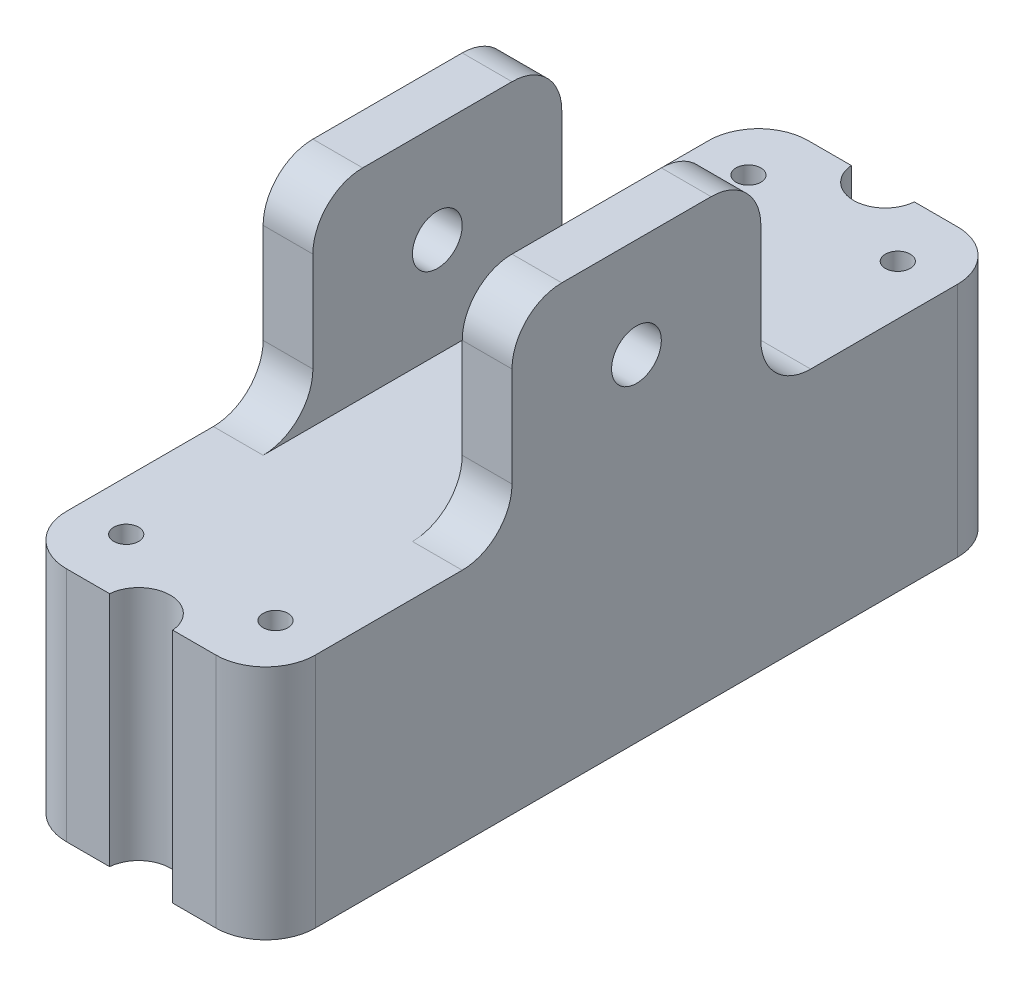
SolidWorks part; units mm, degrees
material "Nylon 101"
ref_plane "Front" through (0, 0, 0) normal (0, 0, 1) x (1, 0, 0)
ref_plane "Top" through (0, 0, 0) normal (0, 1, 0) x (1, 0, 0)
ref_plane "Right" through (0, 0, 0) normal (1, 0, 0) x (0, 0, -1)
sketch "Sketch1" plane through (0, 0, 0) normal (0, 1, 0) x (1, 0, 0)
  line L0 (-25, -75) -> (25, -75) construction
  line L1 (-15, 62.5) -> (15, 62.5) construction
  line L2 (0, -75) -> (0, 75) construction
  line L3 (-25, -75) -> (-25, 75)
  line L4 (25, -75) -> (25, 75)
  line L5 (25, 0) -> (0, 0) construction
  line L6 (25, 17) -> (97.2, 17)
  line L7 (25, 17) -> (25, -17)
  line L8 (25, -17) -> (97.2, -17)
  line L9 (97.2, 17) -> (97.2, -17)
  line L10 (-15, 62.5) -> (-15, -62.5) construction
  line L11 (-15, -62.5) -> (15, -62.5) construction
  line L12 (15, 62.5) -> (15, -62.5) construction
  line L13 (-25, -75.5) -> (25, -75.5)
  line L14 (-25, -74.5) -> (25, -74.5)
  line L15 (-25, 75.5) -> (25, 75.5)
  line L16 (-25, 74.5) -> (25, 74.5)
  circle A0 centre (0, 75) radius 6.35
  circle A1 centre (0, -75) radius 6.35
  arc A2 (-25, -75) -> (25, -75) centre (0, -75) ccw
  arc A3 (25, 75) -> (-25, 75) centre (0, 75) ccw
  circle A6 centre (-15, 62.5) radius 2.5
  circle A7 centre (-15, -62.5) radius 2.5
  circle A8 centre (15, -62.5) radius 2.5
  circle A9 centre (15, 62.5) radius 2.5
  point P8 (0, 0)
  point P24 (0, -62.5)
  dimension "D2" = 12.7
  dimension "D5" = 25
  dimension "D1" = 5
  dimension "D3" = 150
  dimension "D4" = 12.5
  dimension "D6" = 12.5
  dimension "D7" = 34
  dimension "D8" = 72.2
  dimension "D9" = 30
  dimension "D10" = 0.5
  dimension "D11" = 0.5
extrude "Boss-Extrude1" add sketch "Sketch1" along normal blind 10 and the other way blind 37.5 contours A1 L14 L4 L16 A0 L3 A9 A8 A7 A6 region at (0, 0, 0)
sketch "Sketch2" plane through (0, 0, 0) normal (0, 1, 0) x (1, 0, 0)
  line L0 (25, -75) -> (25, 75) construction
  line L1 (25, 25) -> (15, 25)
  line L2 (25, 25) -> (25, -25)
  line L3 (25, -25) -> (15, -25)
  line L4 (15, 25) -> (15, -25)
  line L6 (25, 0) -> (0, 0) construction
  line L7 (25, 0) -> (0, 0) construction
  line L8 (-25, -74.5) -> (-25, 74.5) construction
  line L9 (-25, 25) -> (-15, 25)
  line L10 (-25, 25) -> (-25, -25)
  line L11 (-25, -25) -> (-15, -25)
  line L12 (-15, 25) -> (-15, -25)
  line L13 (0, 0) -> (0, 4.5574) construction
  dimension "D1" = 50
  dimension "D2" = 10
extrude "Boss-Extrude2" add sketch "Sketch2" along normal blind 50
sketch "Sketch4" plane through (25, 0, 0) normal (1, 0, 0) x (0, 0, -1)
  line L0 (-25, 10) -> (25, 10) construction
  line L1 (-74.5, 10) -> (-25, 10) construction
  line L2 (-25, 50) -> (-25, 10) construction
  line L3 (0, 10) -> (0, 50) construction
  line L4 (-25, 50) -> (25, 50) construction
  circle A0 centre (0, 30) radius 5
  dimension "D1" = 10
extrude "Cut-Extrude2" cut sketch "Sketch4" against normal through all
fillet "Fillet1" radius 10 12 edges at (-20, 50, -25) (-20, 50, 25) (-20, 10, 25) (-20, 10, -25) (20, 50, -25) (20, 50, 25) (20, 10, 25) (20, 10, -25) (25, -13.75, -74.5) (-25, -13.75, -74.5) (-25, -13.75, 74.5) (25, -13.75, 74.5)
